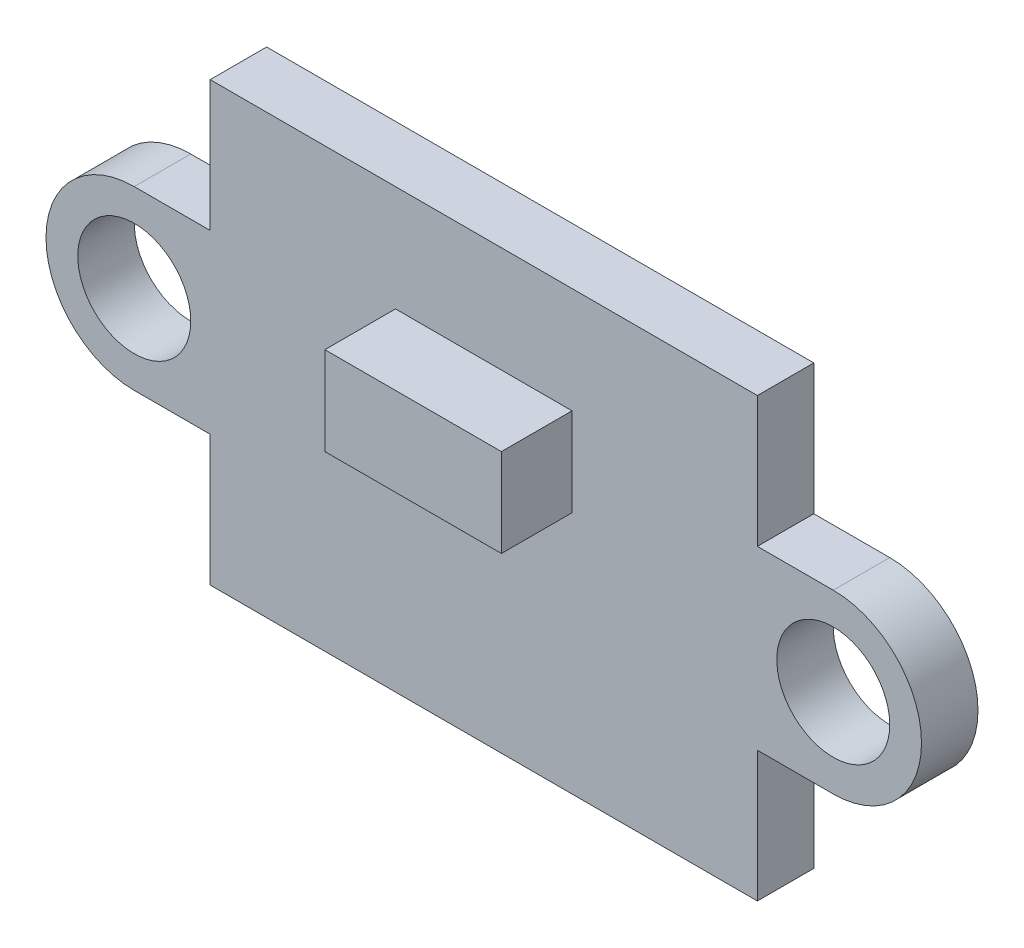
SolidWorks part; units mm, degrees
ref_plane "Front Plane" through (0, 0, 0) normal (0, 0, 1) x (1, 0, 0)
ref_plane "Top Plane" through (0, 0, 0) normal (0, 1, 0) x (1, 0, 0)
ref_plane "Right Plane" through (0, 0, 0) normal (1, 0, 0) x (0, 0, -1)
sketch "Sketch1" plane through (0, 0, 0) normal (0, 0, 1) x (1, 0, 0)
  line L0 (-7.75, 6.2) -> (7.75, 6.2)
  line L1 (7.75, 6.2) -> (7.75, 2.5)
  line L2 (7.75, 2.5) -> (9.9, 2.5)
  line L3 (9.9, -2.5) -> (7.75, -2.5)
  line L4 (7.75, -2.5) -> (7.75, -6.2)
  line L5 (7.75, -6.2) -> (-7.75, -6.2)
  line L6 (-7.75, -6.2) -> (-7.75, -2.5)
  line L7 (-7.75, -2.5) -> (-9.9, -2.5)
  line L8 (-7.75, 6.2) -> (-7.75, 2.5)
  line L9 (-7.75, 2.5) -> (-9.9, 2.5)
  line L10 (-9.9, 0) -> (9.9, 0) construction
  line L11 (-7.75, 6.2) -> (7.75, -6.2) construction
  arc A0 (9.9, 2.5) -> (9.9, -2.5) centre (9.9, 0) cw
  arc A1 (-9.9, 2.5) -> (-9.9, -2.5) centre (-9.9, 0) ccw
  circle A2 centre (-9.9, 0) radius 1.6
  circle A3 centre (9.9, 0) radius 1.6
  point P17 (-0.5364, 6.1018)
  point P18 (0, 0)
  point P20 (7.721, -6.2)
  point P21 (0, 0)
  point P22 (10.3556, 2.5)
  point P23 (-9.6278, 6.2)
  dimension "D2" = 3.2
  dimension "D4" = 2.5
  dimension "D1" = 15.5
  dimension "D3" = 12.4
  dimension "D5" = 19.8
extrude "Boss-Extrude1" add sketch "Sketch1" along normal blind 1.6
sketch "Sketch2" plane through (0, 0, 1.6) normal (0, 0, 1) x (1, 0, 0)
  line L0 (7.75, 6.2) -> (-7.75, 6.2) construction
  line L1 (-2.5, 3.2) -> (2.5, 3.2)
  line L2 (-2.5, 3.2) -> (-2.5, 0.7)
  line L3 (-2.5, 0.7) -> (2.5, 0.7)
  line L4 (2.5, 3.2) -> (2.5, 0.7)
  line L5 (-7.75, 6.2) -> (-7.75, 2.5) construction
  dimension "D1" = 5
  dimension "D2" = 3
  dimension "D3" = 2.5
  dimension "D4" = 5.25
extrude "Boss-Extrude2" add sketch "Sketch2" along normal blind 2
